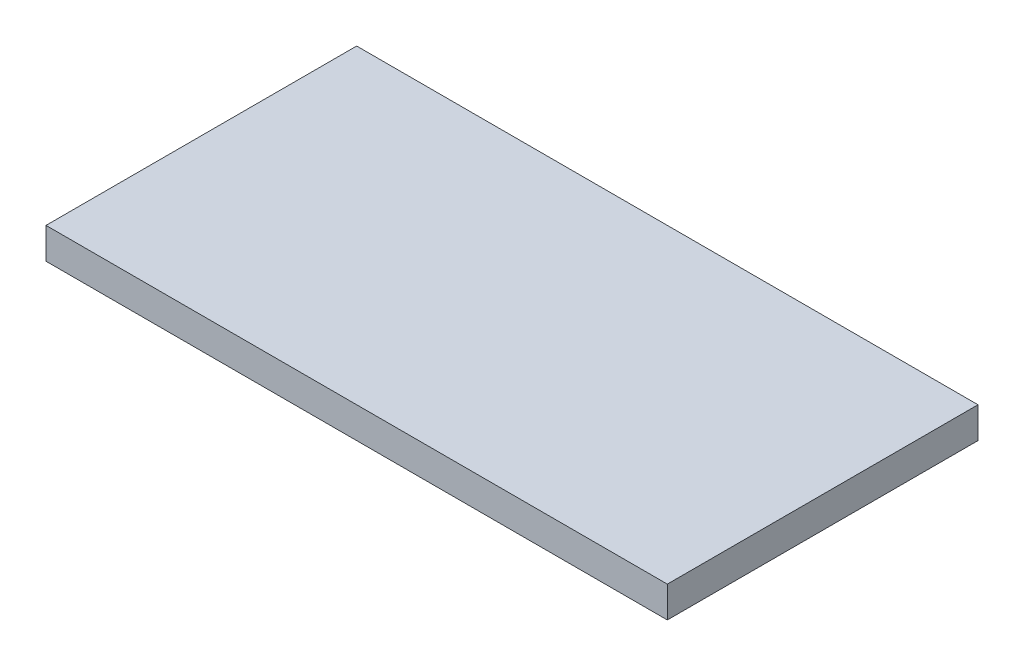
SolidWorks part; units mm, degrees
ref_plane "Front Plane" through (0, 0, 0) normal (0, 0, 1) x (1, 0, 0)
ref_plane "Top Plane" through (0, 0, 0) normal (0, 1, 0) x (1, 0, 0)
ref_plane "Right Plane" through (0, 0, 0) normal (1, 0, 0) x (0, 0, -1)
sketch "Sketch2" plane through (0, 0, 0) normal (0, 1, 0) x (1, 0, 0)
  line L1 (-100, 50) -> (100, 50)
  line L2 (-100, 50) -> (-100, -50)
  line L3 (-100, -50) -> (100, -50)
  line L4 (100, 50) -> (100, -50)
  line L5 (-100, 50) -> (100, -50) construction
  line L6 (-100, -50) -> (100, 50) construction
  point P0 (0, 0)
  dimension "D1" = 200
  dimension "D2" = 100
extrude "Boss-Extrude1" add sketch "Sketch2" along normal blind 10
